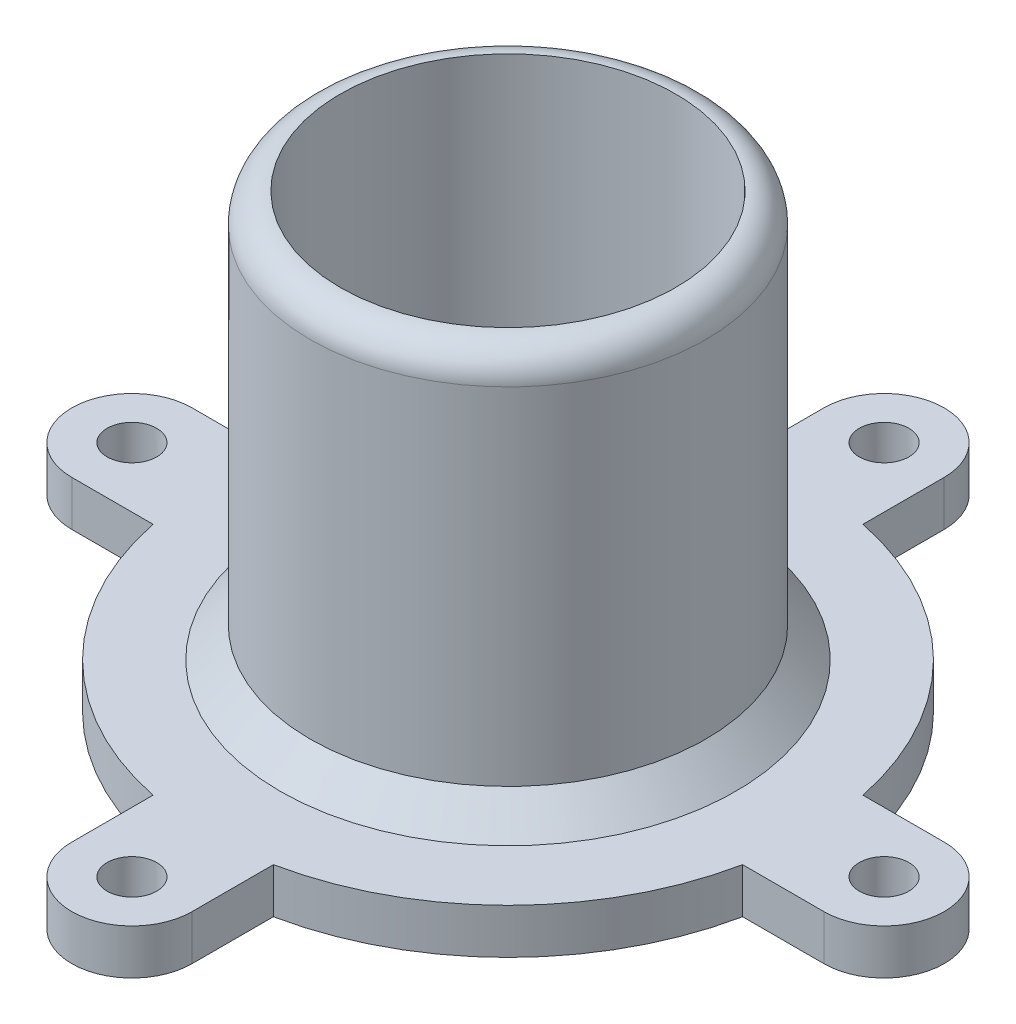
SolidWorks part; units mm, degrees
ref_plane "Alzado" through (0, 0, 0) normal (0, 0, 1) x (1, 0, 0)
ref_plane "Planta" through (0, 0, 0) normal (0, 1, 0) x (1, 0, 0)
ref_plane "Vista lateral" through (0, 0, 0) normal (1, 0, 0) x (0, 0, -1)
sketch "Circunferences" plane through (0, 0, 0) normal (0, 1, 0) x (1, 0, 0)
  circle A0 centre (0, 0) radius 11.15
  circle A1 centre (0, 0) radius 13.15
  circle A2 centre (0, 0) radius 20
  dimension "D1" = 22.3
  dimension "D2" = 26.3
  dimension "D3" = 40
extrude "EXT" add sketch "Circunferences" along normal blind 3 contours A2 A1 region at (-19.4343, 0, 0)
extrude "CENT" add sketch "Circunferences<3>" along normal blind 30 contours A1 A0 region at (-12.7781, 0, 0)
sketch "Circunferences<3>" plane through (0, 0, 0) normal (0, 1, 0) x (1, 0, 0) same geometry as "Circunferences"
sketch "ARMS" plane through (0, 3, 0) normal (0, 1, 0) x (1, 0, 0)
  line L0 (0, 0) -> (20, 0) construction
  line L1 (19.5959, 4) -> (25, 4)
  line L2 (19.5959, -4) -> (25, -4)
  circle A0 centre (0, 0) radius 20 construction
  arc A1 (25, -4) -> (25, 4) centre (25, 0) ccw
  circle A2 centre (25, 0) radius 1.65
  point P10 (22.298, -4)
  circle M4 centre (0, 0) radius 20
  dimension "D3" = 3.3
  dimension "D1" = 8
  dimension "D2" = 25
extrude "ARM" add sketch "ARMS" against normal up to surface (3 mm away) contours L2 A1 L1 A2 M4 region at (22.298, 3, -3.8765) up to face at (0, 0, 20)
pattern_circular "CirPattern1" count 4 over 360 about axis through (0, 3, 0) along (0, 1, 0) of "ARM"
chamfer "Chamfer1" distance 2 angle 45 1 edges at (0, 0, 11.15)
chamfer "Chamfer2" distance 2 angle 45 1 edges at (0, 3, 13.15)
fillet "Fillet1" radius 2 1 edges at (0, 30, 13.15)
equation "\"D2@Circunferences\"=\"D1@Circunferences\"+4"
